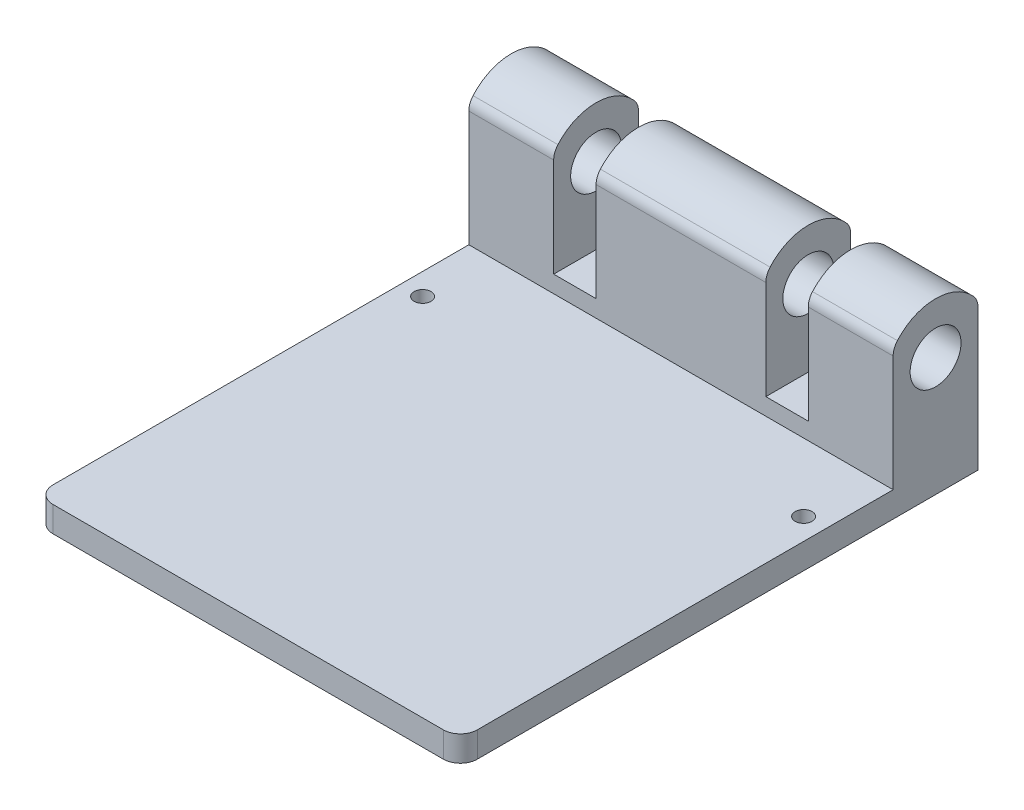
SolidWorks part; units mm, degrees
note: The reader was unsure of these and kept them because the rebuilt part matched: shared geometry of "Sketch3<3>".
ref_plane "Front Plane" through (0, 0, 0) normal (0, 0, 1) x (1, 0, 0)
ref_plane "Top Plane" through (0, 0, 0) normal (0, 1, 0) x (1, 0, 0)
ref_plane "Right Plane" through (0, 0, 0) normal (1, 0, 0) x (0, 0, -1)
sketch "Sketch1" plane through (0, 0, 0) normal (0, 1, 0) x (1, 0, 0)
  line L1 (25, -5) -> (-25, -5)
  line L2 (25, -5) -> (25, 5)
  line L3 (25, 5) -> (-25, 5)
  line L4 (-25, -5) -> (-25, 5)
  line L5 (25, -5) -> (-25, 5) construction
  line L6 (25, 5) -> (-25, -5) construction
  point P0 (0, 0)
  point P7 (0, 0)
  dimension "D1" = 10
  dimension "D2" = 50
extrude "Boss-Extrude1" add sketch "Sketch1" along normal blind 20
sketch "Sketch3" plane through (25, 0, 0) normal (1, 0, 0) x (0, 0, -1)
  line L0 (0, 22.2206) -> (0, -1.7127) construction
  line L1 (5, 20) -> (5, 0) construction
  line L2 (-5, 20) -> (5, 20) construction
  line L4 (-7.7025, 11.0009) -> (8.3941, 11.0009) construction
  arc A0 (5.1967, 11.0009) -> (-5.1967, 11.0009) centre (0, 14) ccw
  circle A1 centre (0, 14) radius 3
  dimension "D2" = 5
  dimension "D3" = 6
  dimension "D1" = 6
  dimension "D4" = 3
extrude "Cut-Extrude1" cut sketch "Sketch3" against normal blind 70
extrude "Cut-Extrude2" cut sketch "Sketch3<3>" against normal blind 70 contours A1
sketch "Sketch3<3>" plane through (25, 0, 0) normal (1, 0, 0) x (0, 0, -1) same geometry as "Sketch3"
sketch "Sketch4" plane through (0, 0, 5) normal (0, 0, 1) x (1, 0, 0)
  line L0 (0, 24.2985) -> (0, -11.4685) construction
  line L2 (-15, 20) -> (-10, 20)
  line L3 (-15, 20) -> (-15, 5)
  line L5 (-10, 20) -> (-10, 5)
  line L6 (-25, 0) -> (25, 0) construction
  line L8 (10, 20) -> (10, 5)
  line L9 (15, 20) -> (10, 20)
  line L10 (15, 20) -> (15, 5)
  line L11 (-15, 5) -> (-10, 5)
  line L12 (10, 5) -> (15, 5)
  dimension "D1" = 5
  dimension "D2" = 10
  dimension "D3" = 15
  dimension "D4" = 5
extrude "Cut-Extrude4" cut sketch "Sketch4" against normal blind 20 contours L3 L11 L5 L2 | L8 L12 L10 L9
fillet "Fillet5" radius 2 1 edges at (-20, 17.3166, 5) type face fillet first side face at (-20, 18.6583, 0) second side face at (0, 10.325, 5)
fillet "Fillet6" radius 2 1 edges at (0, 17.3166, 5) type face fillet first side face at (0, 18.6583, 0) second side face at (0, 10.2132, 5)
fillet "Fillet7" radius 2 1 edges at (20, 17.3166, 5) type face fillet first side face at (20, 18.6583, 0) second side face at (0, 10.1014, 5)
fillet "Fillet8" radius 2 1 edges at (20, 17.3166, -5) type face fillet first side face at (20, 18.8143, -0.3304) second side face at (0, 10.325, -5)
fillet "Fillet9" radius 2 1 edges at (0, 17.3166, -5) type face fillet first side face at (0, 18.8143, -0.3304) second side face at (0, 10.2132, -5)
fillet "Fillet10" radius 2 1 edges at (-20, 17.3166, -5) type face fillet first side face at (-20, 18.8143, -0.3304) second side face at (0, 10.1014, -5)
sketch "Sketch13" plane through (0, 0, 0) normal (0, -1, 0) x (1, 0, 0)
  line L0 (-25, 5) -> (25, 5)
  line L1 (-25, 5) -> (-25, 54)
  line L2 (25, 5) -> (25, 54)
  line L3 (-23, 56) -> (23, 56)
  arc A0 (25, 54) -> (23, 56) centre (23, 54) ccw
  arc A1 (-25, 54) -> (-23, 56) centre (-23, 54) cw
  point P10 (-25, 56)
  dimension "D2" = 2
  dimension "D1" = 51
  dimension "D3" = 50
extrude "Boss-Extrude5" add sketch "Sketch13" against normal blind 3
sketch "Sketch14" plane through (0, 3, 0) normal (0, 1, 0) x (1, 0, 0)
  line L0 (-25, -54) -> (-25, -5) construction
  line L3 (-25, -5) -> (25, -5) construction
  circle A0 centre (-22.45, -13) radius 1
  circle A1 centre (22.45, -13) radius 1
  dimension "D1" = 2
  dimension "D2" = 2
  dimension "D5" = 44.9
  dimension "D6" = 2.55
  dimension "D7" = 8
  dimension "D8" = 8
extrude "Cut-Extrude5" cut sketch "Sketch14" against normal blind 3
